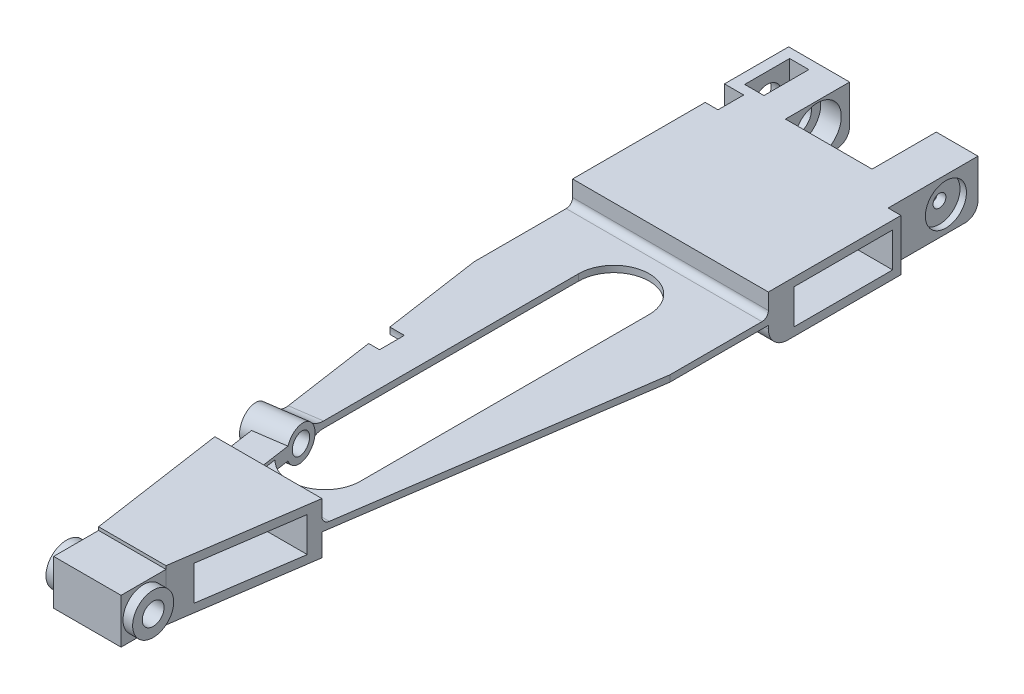
SolidWorks part; units mm, degrees
material "ABS"
ref_plane "Plan de face" through (0, 0, 0) normal (0, 0, 1) x (1, 0, 0)
ref_plane "Plan de dessus" through (0, 0, 0) normal (0, 1, 0) x (1, 0, 0)
ref_plane "Plan de droite" through (0, 0, 0) normal (1, 0, 0) x (0, 0, -1)
sketch "Length" plane through (0, 0, 0) normal (0, 1, 0) x (1, 0, 0)
  line L0 (0, 0) -> (0, 117) construction
  dimension "D1" = 117
sketch "Length2" plane through (0, 0, 0) normal (1, 0, 0) x (0, 0, -1)
  line L0 (100, 0) -> (100, 40) construction
  line L1 (0, 0) -> (117, 0) construction
  dimension "D1" = 40
  dimension "D2" = 100
sketch "Esquisse2" plane through (0, 0, 0) normal (0, 1, 0) x (1, 0, 0)
  line L0 (-6.75, 3.5) -> (-6.75, -3.5)
  line L1 (-6.75, -3.5) -> (6.75, -3.5)
  line L2 (6.75, -3.5) -> (6.75, 3.5)
  line L3 (-6.75, 3.5) -> (6.75, 3.5)
  line L4 (0, -3.5) -> (0, 3.5) construction
  line L5 (0, 0) -> (0, 117) construction
  line L6 (0, 0) -> (6.75, 0) construction
  point P12 (0, 0)
  dimension "D1" = 13.5
  dimension "D2" = 7
extrude "JointTibia" add sketch "Esquisse2" along normal blind 3.5 and the other way blind 3.5
sketch "Esquisse3" plane through (6.75, 0, 0) normal (1, 0, 0) x (0, 0, -1)
  circle A0 centre (0, 0) radius 1.7
  dimension "D1" = 3.4
extrude "HoleAxeTibia" cut sketch "Esquisse3" against normal blind 14.5
sketch "Esquisse4" plane through (6.75, 0, 0) normal (1, 0, 0) x (0, 0, -1)
  circle A0 centre (0, 0) radius 3.2
  circle A1 centre (0, 0) radius 5.5057
  circle A2 centre (0, 0) radius 1.7 construction
extrude "EntretoiseTibia" cut sketch "Esquisse4" against normal blind 1.5
mirror "Symétrie1" about plane through (0, 0, 0) normal (1, 0, 0) of "EntretoiseTibia"
sketch "Esquisse5" plane through (0, 0, 0) normal (0, 1, 0) x (1, 0, 0)
  line L0 (-13.25, 112) -> (-13.25, 122)
  line L1 (-13.25, 122) -> (-6.75, 122)
  line L2 (-6.75, 122) -> (-6.75, 112)
  line L3 (-6.75, 112) -> (6.75, 112)
  line L4 (6.75, 112) -> (6.75, 122)
  line L5 (6.75, 122) -> (13.25, 122)
  line L6 (13.25, 122) -> (13.25, 112)
  line L7 (13.25, 112) -> (13.25, 108)
  line L8 (13.25, 108) -> (-13.25, 108)
  line L9 (-13.25, 108) -> (-13.25, 112)
  line L10 (0, 117) -> (13.25, 117) construction
  line L11 (13.25, 112) -> (6.75, 112) construction
  line L12 (-6.75, 112) -> (-13.25, 112) construction
  line L15 (0, 0) -> (0, 117) construction
  line L16 (-10, 122) -> (-10, 112) construction
  line L17 (10, 122) -> (10, 112) construction
  point P15 (0, 112)
  dimension "D1" = 5
  dimension "D2" = 10
  dimension "D3" = 6.5
  dimension "D4" = 20
  dimension "D5" = 4
extrude "ShapeJointCoxa" add sketch "Esquisse5" along normal blind 4 and the other way blind 4 separate body
sketch "Esquisse6" plane through (13.25, 0, 0) normal (1, 0, 0) x (0, 0, -1)
  line L0 (0, 0) -> (117, 0) construction
  circle A0 centre (117, 0) radius 3.2
  dimension "D1" = 6.4
extrude "HoleMagnet" cut sketch "Esquisse6" against normal blind 1
sketch "Esquisse7" plane through (-13.25, 0, 0) normal (-1, 0, 0) x (0, 0, 1)
  line L0 (0, 0) -> (-117, 0) construction
  circle A0 centre (-117, 0) radius 2.25
  dimension "D1" = 4.5
extrude "HoleAxe" cut sketch "Esquisse7" against normal blind 8
sketch "Esquisse9" plane through (6.75, 0, 0) normal (-1, 0, 0) x (0, 0, 1)
  line L0 (0, 0) -> (-117, 0) construction
  circle A0 centre (-117, 0) radius 3.7
  dimension "D1" = 7.4
extrude "HoleBearing" cut sketch "Esquisse9" against normal blind 3.2
mirror "Symétrie2" about plane through (0, 0, 0) normal (1, 0, 0) of "HoleBearing"
sketch "Esquisse10" plane through (9.95, 0, 0) normal (-1, 0, 0) x (0, 0, 1)
  circle A0 centre (-117, 0) radius 2.25
  circle A1 centre (-117, 0) radius 2.25 construction
extrude "EntretoiseBearing" cut sketch "Esquisse10" against normal blind 1
sketch "Esquisse12" plane through (-13.25, 0, 0) normal (-1, 0, 0) x (0, 0, 1)
  line L0 (-122, -4) -> (-108, -4) construction
  line L1 (-122, 4) -> (-112, 4)
  line L2 (-122, 4) -> (-122, -4)
  line L3 (-122, -4) -> (-112, -4)
  line L4 (-112, 4) -> (-112, -4)
  circle A0 centre (-117, 0) radius 2.25
  circle A1 centre (-117, 0) radius 2.25 construction
extrude "ExtScrewLess" add sketch "Esquisse12" along normal blind 3
sketch "Esquisse13" plane through (0, 4, 0) normal (0, 1, 0) x (1, 0, 0)
  line L0 (-6.75, 112) -> (-13.25, 112) construction
  line L1 (-9.95, 122) -> (-9.95, 112) construction
  line L2 (-6.75, 122) -> (-16.25, 122) construction
  line L4 (-9.95, 113.3) -> (-9.95, 120.7) construction
  line L5 (-9.95, 117) -> (-16.25, 117) construction
  line L6 (-16.25, 112) -> (-16.25, 122) construction
  line L8 (-14.6, 113.5) -> (-11.6, 113.5)
  line L9 (-14.6, 113.5) -> (-14.6, 120.5)
  line L10 (-14.6, 120.5) -> (-11.6, 120.5)
  line L11 (-11.6, 113.5) -> (-11.6, 120.5)
  line L12 (-14.6, 113.5) -> (-11.6, 120.5) construction
  line L13 (-14.6, 120.5) -> (-11.6, 113.5) construction
  point P14 (-13.1, 117)
  dimension "D1" = 3
  dimension "D2" = 7
extrude "ScewLessLocker" cut sketch "Esquisse13" against normal blind 10
sketch "Esquisse24" plane through (0, 0, -108) normal (0, 0, 1) x (1, 0, 0)
  line L0 (-13.25, 4) -> (13.25, 4) construction
  line L1 (15.25, -4) -> (-15.25, -4)
  line L2 (15.25, -4) -> (15.25, 4)
  line L3 (15.25, 4) -> (-15.25, 4)
  line L4 (-15.25, -4) -> (-15.25, 4)
  line L5 (15.25, -4) -> (-15.25, 4) construction
  line L6 (15.25, 4) -> (-15.25, -4) construction
  line L7 (13.25, -4) -> (13.25, 4) construction
  point P0 (0, 0)
  dimension "D1" = 2
extrude "Shape_bdy" add sketch "Esquisse24" along normal up to surface (104.5 mm away) up to face at (0, 0, -3.5)
sketch "Esquisse26" plane through (0, -4, 0) normal (0, -1, 0) x (1, 0, 0)
  line L0 (-5.25, -3.5) -> (-15.25, -72)
  line L2 (-15.25, -72) -> (-15.25, -3.5)
  line L3 (-15.25, -3.5) -> (-5.25, -3.5)
  line L4 (5.25, -3.5) -> (15.25, -3.5)
  line L5 (15.25, -3.5) -> (15.25, -72)
  line L7 (15.25, -72) -> (5.25, -3.5)
  line L8 (-15.25, -72) -> (15.25, -72) construction
  line L9 (15.25, -3.5) -> (15.25, -108) construction
  line L10 (-16.25, -112) -> (-13.25, -112) construction
  line L11 (-15.25, -3.5) -> (-15.25, -108) construction
  line L12 (-15.25, -3.5) -> (15.25, -3.5) construction
  point P16 (-14.75, -112)
  dimension "D1" = 40
extrude "Triangulize" cut sketch "Esquisse26" against normal blind 10
sketch "Esquisse27" plane through (15.25, 0, 0) normal (1, 0, 0) x (0, 0, -1)
  line L0 (0, 0) -> (117, 0) construction
  line L1 (91.3, -2.7) -> (106.7, -2.7)
  line L2 (91.3, -2.7) -> (91.3, 2.7)
  line L3 (91.3, 2.7) -> (106.7, 2.7)
  line L4 (106.7, -2.7) -> (106.7, 2.7)
  line L5 (91.3, -2.7) -> (106.7, 2.7) construction
  line L6 (91.3, 2.7) -> (106.7, -2.7) construction
  line L8 (7.3, -2.7) -> (22.7, -2.7)
  line L9 (7.3, -2.7) -> (7.3, 2.7)
  line L10 (7.3, 2.7) -> (22.7, 2.7)
  line L11 (22.7, -2.7) -> (22.7, 2.7)
  line L12 (7.3, -2.7) -> (22.7, 2.7) construction
  line L13 (7.3, 2.7) -> (22.7, -2.7) construction
  circle A0 centre (117, 0) radius 3.2 construction
  point P0 (99, 0)
  point P7 (15, 0)
  dimension "D1" = 15.4
  dimension "D2" = 5.4
  dimension "D3" = 15
  dimension "D5" = 84
  dimension "D4" = 18
extrude "AttachWings" cut sketch "Esquisse27" against normal blind 10
mirror "Symétrie4" about plane through (0, 0, 0) normal (1, 0, 0) of "AttachWings"
sketch "Esquisse29" plane through (15.25, 0, 0) normal (1, 0, 0) x (0, 0, -1)
  line L0 (7.3, 2.7) -> (22.7, -2.7) construction
  line L1 (91.3, 2.7) -> (106.7, -2.7) construction
  line L2 (15, 0) -> (99, 0) construction
  line L3 (15, 0) -> (15, 0.5) construction
  line L4 (15, 0.5) -> (99, 0.5) construction
  line L5 (99, 0.5) -> (99, 0) construction
  line L6 (99, 0) -> (99, -0.5) construction
  line L7 (99, -0.5) -> (15, -0.5) construction
  line L8 (15, -0.5) -> (15, 0) construction
  line L9 (56.0231, 10.2008) -> (56.0231, -10.2008) construction
  line L10 (24.7035, 0.5) -> (87.3427, 0.5)
  line L11 (24.7035, 0.5) -> (24.7035, 10.2008)
  line L12 (24.7035, 10.2008) -> (87.3427, 10.2008)
  line L13 (87.3427, 0.5) -> (87.3427, 10.2008)
  line L14 (24.7035, -0.5) -> (87.3427, -0.5)
  line L15 (24.7035, -0.5) -> (24.7035, -10.2008)
  line L16 (24.7035, -10.2008) -> (87.3427, -10.2008)
  line L17 (87.3427, -0.5) -> (87.3427, -10.2008)
  dimension "D1" = 1
extrude "Void body" cut sketch "Esquisse29" against normal blind 38
sketch "Esquisse30" plane through (0, 0.5, 0) normal (0, 1, 0) x (1, 0, 0)
  line L0 (0, 24.7035) -> (0, 87.3427) construction
  line L1 (-8.3454, 24.7035) -> (8.3454, 24.7035) construction
  line L2 (-15.25, 87.3427) -> (15.25, 87.3427) construction
  line L3 (0, 78.5231) -> (0, 33.5231) construction
  line L4 (5.5, 78.5231) -> (5.5, 33.5231)
  line L5 (-5.5, 78.5231) -> (-5.5, 33.5231)
  arc A0 (5.5, 78.5231) -> (-5.5, 78.5231) centre (0, 78.5231) ccw
  arc A1 (-5.5, 33.5231) -> (5.5, 33.5231) centre (0, 33.5231) ccw
  point P8 (0, 56.0231)
  dimension "D1" = 11
  dimension "D2" = 45
extrude "Mass remover & PCB" cut sketch "Esquisse30" against normal blind 10
fillet "Congé1" radius 5 1 edges at (0, -4, -112)
fillet "Congé2" radius 3 1 edges at (0, -4, -87.3427)
sketch "Esquisse32" plane through (5.25, 0, 0) normal (1, 0, 0) x (0, 0, -1)
  line L1 (106.7, -2.7) -> (91.3, -2.7)
  line L2 (106.7, -2.7) -> (106.7, 2.7)
  line L3 (106.7, 2.7) -> (91.3, 2.7)
  line L4 (91.3, -2.7) -> (91.3, 2.7)
  line L5 (22.7, -2.7) -> (7.3, -2.7)
  line L6 (22.7, -2.7) -> (22.7, 2.7)
  line L7 (22.7, 2.7) -> (7.3, 2.7)
  line L8 (7.3, -2.7) -> (7.3, 2.7)
extrude "LockerHole" cut sketch "Esquisse32" against normal blind 32
sketch "Esquisse33" plane through (-4.6402, 0, 0.6774) normal (-0.9895, 0, 0.1445) x (0.1445, 0, 0.9895)
  line L0 (-25.6499, -0.5) -> (-25.6499, 0.5) construction
  line L1 (-25.6499, 0) -> (-34.8151, 0) construction
  line L2 (-0.9751, 0) -> (-34.8151, 0) construction
  circle A0 centre (-34.8151, 0) radius 2.6
  ellipse E1 centre (-0.9751, 0) end of major axis (-0.9751, 1.7) minor radius 1.6822 construction
  dimension "D3" = 5.2
  dimension "D1" = 33.84
extrude "FixationSensor" add sketch "Esquisse33" against normal blind 5 and the other way blind 1.5
sketch "Esquisse34" plane through (-6.1244, 0, 0.8941) normal (-0.9895, 0, 0.1445) x (0.1445, 0, 0.9895)
  circle A0 centre (-34.8151, 0) radius 1.6
  dimension "D1" = 3.2
extrude "ScrewFixationSensor" cut sketch "Esquisse34" against normal blind 10
sketch "Esquisse35" plane through (-4.6402, 0, 0.6774) normal (-0.9895, 0, 0.1445) x (0.1445, 0, 0.9895)
  line L0 (-32.4151, -1) -> (-24.4151, -1)
  line L1 (-32.4151, 1) -> (-24.4151, 1)
  line L2 (-32.4151, -1) -> (-32.4151, 1)
  line L3 (-24.4151, 1) -> (-24.4151, -1)
  line L4 (-32.4151, 0) -> (-24.4151, 0) construction
  line L5 (-28.4151, 0) -> (-28.4151, -1) construction
  line L6 (-28.4151, 0) -> (-28.4151, 1) construction
  circle A0 centre (-34.8151, 0) radius 2.6 construction
  dimension "D1" = 2
  dimension "D2" = 8
extrude "FixationSensorRenfor" add sketch "Esquisse35" against normal up to surface (5 mm away) up to face at (-4.4907, 0, -32.9116)
fillet "Congé3" radius 3 2 edges at (-7.769, 0.5, -36.6285) (-7.769, -0.5, -36.6285)
fillet "Congé4" radius 2 2 edges at (10, -4, -122) (-11.5, -4, -122)
fillet "Congé5" radius 2 2 edges at (-5.8189, 1, -24.7035) (-5.8189, -1, -24.7035)
fillet "Congé6" radius 1 2 edges at (0, 0.5, -87.3427) (2.5265, 0.5, -24.7035)
sketch "Esquisse36" plane through (-15.25, 0, 0) normal (-1, 0, 0) x (0, 0, 1)
  line L0 (-22.7, 2.7) -> (-22.7, -2.7) construction
  circle A0 centre (-54.7, 0) radius 2
  dimension "D1" = 32
  dimension "D2" = 4
extrude "Enlèv. mat.-Extru.1" cut sketch "Esquisse36" against normal blind 4.5
sketch "Esquisse38" plane through (12.25, 0, 0) normal (1, 0, 0) x (0, 0, -1)
  circle A0 centre (117, 0) radius 1
  dimension "D1" = 2
extrude "Remover helper" cut sketch "Esquisse38" against normal blind 10
equation "\"entretoiseBearing\"= 1.5mm"
equation "\"length_tibia\"= 206mm"
equation "\"length_femur\"= 117mm"
equation "\"length_coxa\"= 27mm"
equation "\"D1@Esquisse4\"=\"entretoiseBearing\""
equation "\"height\"= 40mm"
equation "\"width\"= 100mm"
equation "\"lever\"= 40mm"
equation "\"depthMagnet\"= 1mm"
equation "\"D1@HoleMagnet\"=\"depthMagnet\""
equation "\"D1@Esquisse7\"=\"entretoiseBearing\"+3"
equation "\"D1@Length\"=\"length_femur\""
equation "\"D1@Length2\"=\"height\""
equation "\"D2@Length2\"=\"width\""
equation "\"D1@Ref\"= \"length_femur\""
equation "\"errorFlat\"= 0.20mm"
equation "\"errorCircle\"= 0.40mm"
equation "\"D2@Esquisse27\"= 5.00mm+2*\"errorFlat\""
equation "\"D1@Esquisse27\"= 15.00mm + 2*\"errorFlat\""
equation "\"cuticule\"=1.5mm"
equation "\"cuticule_attach_w\"=10mm"
equation "\"cuticule_attach_h\"=2.5mm"
equation "\"D1@Esquisse3\"=\"errorCircle\"+3"
equation "\"D1@Esquisse9\"=\"errorCircle\"+7"
equation "\"D1@HoleBearing\"=\"errorFlat\"+3"
equation "\"D1@Esquisse2\"=13.50mm"
equation "\"D1@Esquisse6\"= 6 +\"errorCircle\""
equation "\"errorFlat_tight\"= 0.15mm"
equation "\"errorCircle_tight\" = 0.30mm"
equation "\"insert_d\" = 3.2mm"
equation "\"insert_l\" = 5mm"
equation "\"D1@Esquisse34\"= \"insert_d\""
equation "\"D2@FixationSensor\"= \"cuticule\""
equation "\"D1@FixationSensor\"= \"insert_l\""
equation "\"D3@Esquisse33\"= \"insert_d\" + 2"
equation "\"D1@Esquisse33\"= 34.24mm - \"errorCircle\""
